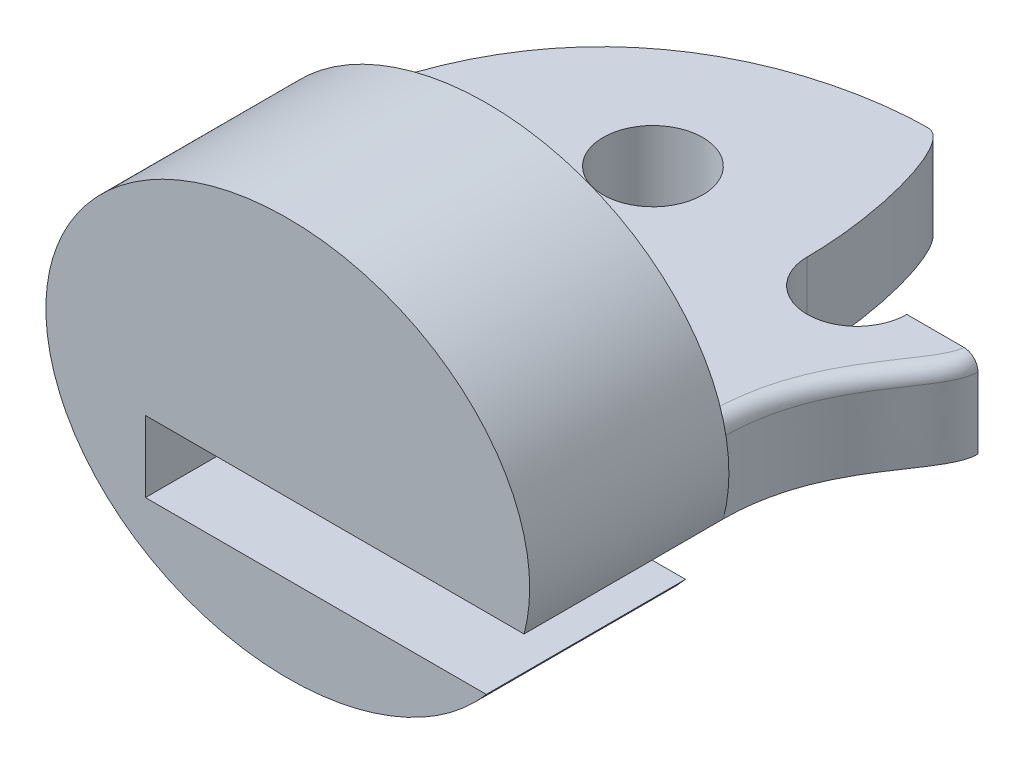
SolidWorks part; units mm, degrees
ref_plane "Front Plane" through (0, 0, 0) normal (0, 0, 1) x (1, 0, 0)
ref_plane "Top Plane" through (0, 0, 0) normal (0, 1, 0) x (1, 0, 0)
ref_plane "Right Plane" through (0, 0, 0) normal (1, 0, 0) x (0, 0, -1)
sketch "Sketch1" plane through (0, 0, 0) normal (0, 0, 1) x (1, 0, 0)
  ellipse E0 centre (0, 0) end of major axis (8.5, 0) minor radius 7
  dimension "D1" = 17
  dimension "D2" = 14
extrude "Boss-Extrude1" add sketch "Sketch1" along normal blind 7
sketch "Sketch3" plane through (0, 0, 7) normal (0, 0, 1) x (1, 0, 0)
  line L0 (-5, -4) -> (8.3026, -4)
  line L1 (0, -7) -> (0, -4) construction
  line L2 (8.3026, -4) -> (8.3026, -1.5)
  line L3 (8.3026, -1.5) -> (-5, -1.5)
  line L4 (-5, -1.5) -> (-5, -4)
  line L5 (-8.5, 0) -> (-8.5, -8.3755) construction
  line L6 (-8.5, 0) -> (-8.5, -3.4042) construction
  ellipse E0 centre (0, 0) end of major axis (8.5, 0) minor radius 7 construction
  dimension "D1" = 3
  dimension "D2" = 2.5
  dimension "D3" = 3.5
  dimension "D4" = 0
extrude "Cut-Extrude1" cut sketch "Sketch3" against normal blind 7
ref_plane "Plane1" through (0, -1.5, 0) normal (0, -1, 0) x (-1, 0, 0)
sketch "Sketch4" plane through (0, -1.5, 0) normal (0, -1, 0) x (-1, 0, 0)
  line L0 (8.5, 0) -> (-3, 0) construction
  line L2 (5, 0) -> (-6.9755, 0) construction
  line L3 (-3, 0) -> (-3, 12.5) construction
  line L4 (-8.3026, 0) -> (-6.5526, 0) construction
  line L5 (-6.5526, 0) -> (-6.5526, 6.45) construction
  line L6 (8.5, 0) -> (0.67, 0) construction
  line L7 (0.67, 0) -> (0.67, 6.5) construction
  line L8 (8.5, 0) -> (5.5, 0) construction
  line L9 (5.5, 0) -> (5.5, 3) construction
  line L10 (-4.8026, 6.45) -> (-8.3026, 6.45) construction
  line L11 (-8.3026, 6.45) -> (-10.8026, 6.45)
  line L12 (8.5, 0) -> (-8.3026, 0)
  arc A0 (-8.3026, 6.45) -> (-4.8026, 6.45) centre (-6.5526, 6.45) ccw
  circle A1 centre (0.67, 6.5) radius 1.75
  circle A2 centre (5.5, 3) radius 1.75
  spline S0 degree 3 poles (-4.8026, 6.45) (-4.8026, 9.0553) (-3.8761, 12.5) (-3, 12.5) knots 0 0 0 0 0.703518 0.703518 0.703518 0.703518
  spline S1 degree 3 poles (8.5, 0) (8.5, 10.6134) (0.4609, 12.5) (-3, 12.5) knots 0 0 0 0 0.609858 0.609858 0.609858 0.609858
  spline S2 degree 3 poles (-8.3026, 0) (-8.3026, 3.5755) (-10.8026, 5.1353) (-10.8026, 6.45) knots 0 0 0 0 0.745481 0.745481 0.745481 0.745481
  dimension "D9" = 3.5
  dimension "D10" = 3.5
  dimension "D11" = 3.5
  dimension "D1" = 11.5
  dimension "D2" = 12.5
  dimension "D3" = 1.75
  dimension "D4" = 6.45
  dimension "D5" = 7.83
  dimension "D6" = 6.5
  dimension "D7" = 3
  dimension "D8" = 3
  dimension "D12" = 2.5
  dimension "D13" = 7.2226
extrude "Boss-Extrude3" add sketch "Sketch4" against normal blind 3
sketch "Sketch5" plane through (0, 0, 0) normal (0, 0, -1) x (-1, 0, 0)
  line L0 (7.7159, 2.9365) -> (9.4185, 2.9365)
  line L1 (9.4185, 2.9365) -> (9.4185, -1.0695)
  line L2 (9.4185, -1.0695) -> (8.4002, -1.0695)
  ellipse E0 centre (0, 0) end of major axis (8.5, 0) minor radius 7 (8.4002, -1.0695) -> (7.7159, 2.9365) ccw
extrude "Cut-Extrude2" cut sketch "Sketch5" along normal blind 10
fillet "Fillet1" radius 0.5 1 edges
sketch "Sketch8" plane through (0, 0, 0) normal (0, 1, 0) x (1, 0, 0)
  line L0 (6.5526, 6.45) -> (-0.67, 6.5) construction
  line L2 (-8.5, -7) -> (8.5, -7) construction
  line L3 (-8.5, 0) -> (-7.4103, 0) construction
  line L4 (-8.5, 0) -> (-8.5, -7) construction
  line L5 (-8.5, -7) -> (-7.4103, -7) construction
  line L6 (-7.4103, 0) -> (-7.4103, -7) construction
  arc A0 (4.8026, 6.45) -> (8.3026, 6.45) centre (6.5526, 6.45) ccw construction
  circle A1 centre (-0.67, 6.5) radius 1.75 construction
  arc A2 (4.8026, 6.45) -> (8.3026, 6.45) centre (6.5526, 6.45) ccw construction
  circle A3 centre (-0.67, 6.5) radius 1.75 construction
  dimension "D1" = 7.83
sketch "Sketch9" plane through (0, -1.5, 0) normal (0, -1, 0) x (1, 0, 0)
  line L0 (-5.5, -3) -> (-5.5, 7) construction
  line L1 (8.5, 7) -> (-8.5, 7) construction
scale "Scale1" scale about centroid uniform scaling yes scale factor 2
